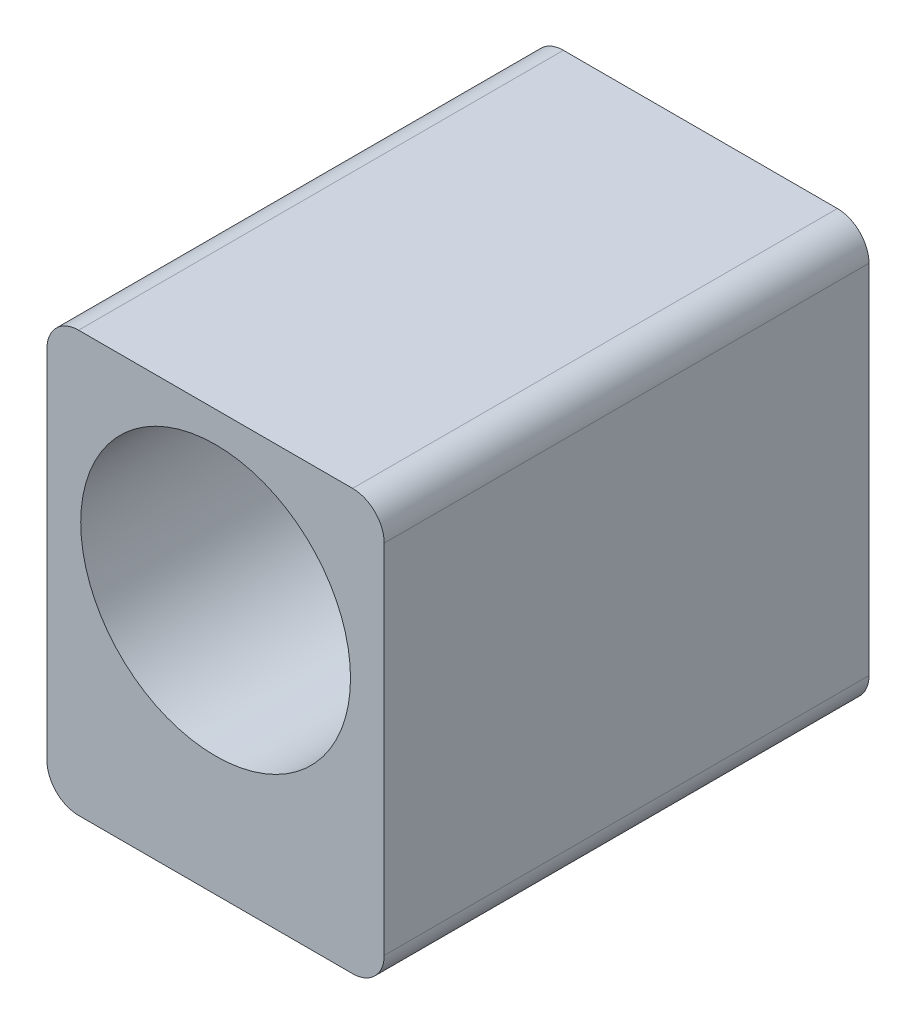
SolidWorks part; units mm, degrees
ref_plane "Front Plane" through (0, 0, 0) normal (0, 0, 1) x (1, 0, 0)
ref_plane "Top Plane" through (0, 0, 0) normal (0, 1, 0) x (1, 0, 0)
ref_plane "Right Plane" through (0, 0, 0) normal (1, 0, 0) x (0, 0, -1)
sketch "Sketch1" plane through (0, 0, 0) normal (0, 0, 1) x (1, 0, 0)
  line L0 (-13, -24.182) -> (13, -24.182)
  line L1 (16, -21.182) -> (16, 12.7)
  line L2 (13, 15.7) -> (-13, 15.7)
  line L3 (-16, 12.7) -> (-16, -21.182)
  arc A0 (13, -24.182) -> (16, -21.182) centre (13, -21.182) ccw
  arc A1 (16, 12.7) -> (13, 15.7) centre (13, 12.7) ccw
  arc A2 (-13, 15.7) -> (-16, 12.7) centre (-13, 12.7) ccw
  arc A3 (-16, -21.182) -> (-13, -24.182) centre (-13, -21.182) ccw
  circle A4 centre (0, 0) radius 12.8
extrude "Boss-Extrude1" add sketch "Sketch1" along normal mid plane 46
ref_plane "Plane1" through (0, -24.182, 0) normal (0, 1, 0) x (1, 0, 0)
sketch "Sketch2" plane through (0, -24.182, 0) normal (0, 1, 0) x (1, 0, 0)
  circle A0 centre (12, -17.5) radius 2
  circle A1 centre (-12, 17.5) radius 2
extrude "Cut-Extrude1" cut sketch "Sketch2" along normal blind 9
